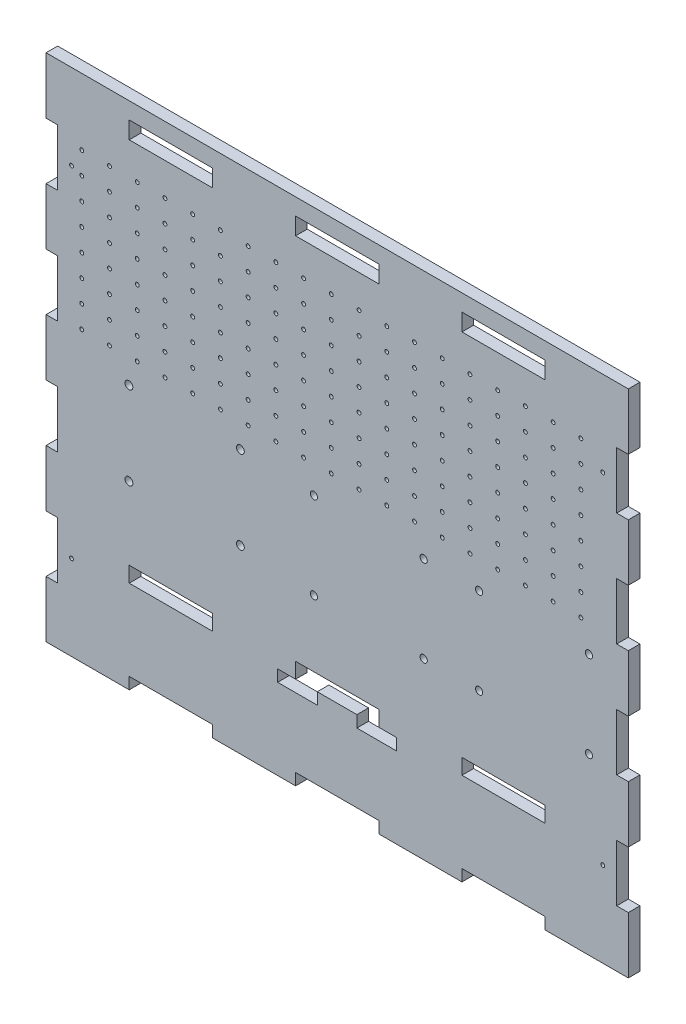
SolidWorks part; units mm, degrees
ref_plane "Front Plane" through (0, 0, 0) normal (0, 0, 1) x (1, 0, 0)
ref_plane "Top Plane" through (0, 0, 0) normal (0, 1, 0) x (1, 0, 0)
ref_plane "Right Plane" through (0, 0, 0) normal (1, 0, 0) x (0, 0, -1)
sketch "Sketch1" plane through (0, 0, 0) normal (0, 0, 1) x (1, 0, 0)
  line L1 (-127.8759, 139.2641) -> (138.8241, 139.2641)
  line L2 (-127.8759, 139.2641) -> (-127.8759, -84.2559)
  line L3 (-127.8759, -84.2559) -> (138.8241, -84.2559)
  line L4 (138.8241, 139.2641) -> (138.8241, -84.2559)
  dimension "D1" = 266.7
  dimension "D2" = 223.52
extrude "Boss-Extrude1" add sketch "Sketch1" along normal blind 5.334
sketch "Sketch2" plane through (0, 0, 5.334) normal (0, 0, 1) x (1, 0, 0)
  line L0 (-127.8759, -84.2559) -> (138.8241, -84.2559) construction
  line L1 (-89.7759, -84.2559) -> (-51.6759, -84.2559)
  line L2 (-89.7759, -84.2559) -> (-89.7759, -78.9219)
  line L3 (-89.7759, -78.9219) -> (-51.6759, -78.9219)
  line L4 (-51.6759, -84.2559) -> (-51.6759, -78.9219)
  line L5 (-89.7759, -78.9219) -> (-127.8759, -78.9219) construction
  line L6 (-13.5759, -84.2559) -> (24.5241, -84.2559)
  line L7 (-13.5759, -84.2559) -> (-13.5759, -78.9219)
  line L8 (-13.5759, -78.9219) -> (24.5241, -78.9219)
  line L9 (24.5241, -84.2559) -> (24.5241, -78.9219)
  line L10 (62.6241, -84.2559) -> (100.7241, -84.2559)
  line L11 (62.6241, -84.2559) -> (62.6241, -78.9219)
  line L12 (62.6241, -78.9219) -> (100.7241, -78.9219)
  line L13 (100.7241, -84.2559) -> (100.7241, -78.9219)
  line L14 (-127.8759, 139.2641) -> (-127.8759, -84.2559) construction
  line L15 (-51.6759, -78.9219) -> (-13.5759, -78.9219) construction
  line L16 (24.5241, -78.9219) -> (62.6241, -78.9219) construction
  line L17 (62.6241, -78.9219) -> (62.364, -79.7896) construction
  line L18 (100.7241, -78.9219) -> (138.8241, -78.9219) construction
  line L19 (138.8241, -84.2559) -> (138.8241, 139.2641) construction
  line L20 (-127.8759, 27.5041) -> (138.8241, 27.5041) construction
  line L21 (100.7241, 139.2641) -> (100.7241, 133.9301)
  line L22 (62.6241, 133.9301) -> (100.7241, 133.9301)
  line L23 (62.6241, 139.2641) -> (62.6241, 133.9301)
  line L24 (24.5241, 139.2641) -> (24.5241, 133.9301)
  line L25 (-13.5759, 133.9301) -> (24.5241, 133.9301)
  line L26 (-13.5759, 139.2641) -> (-13.5759, 133.9301)
  line L27 (-51.6759, 139.2641) -> (-51.6759, 133.9301)
  line L28 (-89.7759, 133.9301) -> (-51.6759, 133.9301)
  line L29 (-89.7759, 139.2641) -> (-89.7759, 133.9301)
  line L30 (62.6241, 139.2641) -> (100.7241, 139.2641)
  line L31 (-13.5759, 139.2641) -> (24.5241, 139.2641)
  line L32 (-89.7759, 139.2641) -> (-51.6759, 139.2641)
  dimension "D1" = 5.334
extrude "Cut-Extrude1" cut sketch "Sketch2" against normal through all
sketch "Sketch5" plane through (0, 0, 5.334) normal (0, 0, 1) x (1, 0, 0)
  line L0 (-51.6759, -34.8224) -> (-13.5759, -34.8224) construction
  line L1 (-89.7759, -34.8224) -> (-51.6759, -34.8224)
  line L2 (-89.7759, -34.8224) -> (-89.7759, -41.9344)
  line L3 (-89.7759, -41.9344) -> (-51.6759, -41.9344)
  line L4 (-51.6759, -34.8224) -> (-51.6759, -41.9344)
  line L5 (-13.5759, -34.8224) -> (24.5241, -34.8224)
  line L6 (-13.5759, -34.8224) -> (-13.5759, -41.9344)
  line L7 (-13.5759, -41.9344) -> (24.5241, -41.9344)
  line L8 (24.5241, -34.8224) -> (24.5241, -41.9344)
  line L9 (62.6241, -34.8224) -> (100.7241, -34.8224)
  line L10 (62.6241, -34.8224) -> (62.6241, -41.9344)
  line L11 (62.6241, -41.9344) -> (100.7241, -41.9344)
  line L12 (100.7241, -34.8224) -> (100.7241, -41.9344)
  line L13 (-51.6759, -41.9344) -> (-13.5759, -41.9344) construction
  line L14 (24.5241, -34.8224) -> (62.6241, -34.8224) construction
  line L15 (24.5241, -41.9344) -> (62.6241, -41.9344) construction
  line L16 (-89.7759, -34.8224) -> (-127.8759, -34.8224) construction
  line L17 (-127.8759, 139.2641) -> (-127.8759, -84.2559) construction
  line L18 (-89.7759, -41.9344) -> (-127.8759, -41.9344) construction
  line L19 (100.7241, -34.8224) -> (138.8241, -34.8224) construction
  line L20 (138.8241, -84.2559) -> (138.8241, 139.2641) construction
  line L21 (100.7241, -41.9344) -> (138.8241, -41.9344) construction
  dimension "D1" = 7.112
extrude "Cut-Extrude3" cut sketch "Sketch5" against normal through all
sketch "Sketch8" plane through (0, 0, 5.334) normal (0, 0, 1) x (1, 0, 0)
  line L0 (-13.5759, -41.9344) -> (24.5241, -41.9344) construction
  line L1 (-21.7977, -47.2684) -> (-3.6478, -47.2684)
  line L2 (-21.7977, -47.2684) -> (-21.7977, -41.9344)
  line L3 (-21.7977, -41.9344) -> (-3.6478, -41.9344)
  line L4 (-3.6478, -47.2684) -> (-3.6478, -41.9344)
  line L5 (-3.6478, -47.2684) -> (14.5022, -47.2684) construction
  line L6 (14.5022, -41.9344) -> (32.6521, -41.9344)
  line L7 (14.5022, -41.9344) -> (14.5022, -47.2684)
  line L8 (14.5022, -47.2684) -> (32.6521, -47.2684)
  line L9 (32.6521, -41.9344) -> (32.6521, -47.2684)
  line L10 (14.5022, -47.2684) -> (14.3218, -49.4005) construction
  line L11 (14.5022, -41.9344) -> (-3.6478, -41.9344) construction
  line L12 (62.6241, -34.8224) -> (62.6241, -41.9344) construction
  line L13 (-51.6759, -41.9344) -> (-51.6759, -34.8224) construction
  dimension "D1" = 5.334
  dimension "D2" = 29.972
  dimension "D3" = 29.8782
extrude "Cut-Extrude6" cut sketch "Sketch8" against normal through all
sketch "Sketch9" plane through (0, 0, 5.334) normal (0, 0, 1) x (1, 0, 0)
  line L0 (-111.5143, 118.9789) -> (-98.8143, 118.9789) construction
  line L1 (-111.5143, 108.8189) -> (-98.8143, 108.8189) construction
  line L2 (-111.5143, 98.6589) -> (-98.8143, 98.6589) construction
  line L3 (-111.5143, 88.4989) -> (-98.8143, 88.4989) construction
  line L4 (-111.5143, 78.3389) -> (-98.8143, 78.3389) construction
  line L5 (-111.5143, 68.1789) -> (-98.8143, 68.1789) construction
  line L6 (-111.5143, 58.0189) -> (-98.8143, 58.0189) construction
  line L7 (-111.5143, 47.8589) -> (-98.8143, 47.8589) construction
  line L8 (-111.5143, 118.9789) -> (-111.5143, 108.8189) construction
  circle A0 centre (-111.5143, 118.9789) radius 0.889
  circle A1 centre (-98.8143, 118.9789) radius 0.889
  circle A2 centre (-86.1143, 118.9789) radius 0.889
  circle A3 centre (-73.4143, 118.9789) radius 0.889
  circle A4 centre (-60.7143, 118.9789) radius 0.889
  circle A5 centre (-48.0143, 118.9789) radius 0.889
  circle A6 centre (-35.3143, 118.9789) radius 0.889
  circle A7 centre (-22.6143, 118.9789) radius 0.889
  circle A8 centre (-9.9143, 118.9789) radius 0.889
  circle A9 centre (2.7857, 118.9789) radius 0.889
  circle A10 centre (15.4857, 118.9789) radius 0.889
  circle A11 centre (28.1857, 118.9789) radius 0.889
  circle A12 centre (40.8857, 118.9789) radius 0.889
  circle A13 centre (53.5857, 118.9789) radius 0.889
  circle A14 centre (66.2857, 118.9789) radius 0.889
  circle A15 centre (78.9857, 118.9789) radius 0.889
  circle A16 centre (91.6857, 118.9789) radius 0.889
  circle A17 centre (104.3857, 118.9789) radius 0.889
  circle A18 centre (117.0857, 118.9789) radius 0.889
  circle A19 centre (-111.5143, 108.8189) radius 0.889
  circle A20 centre (-98.8143, 108.8189) radius 0.889
  circle A21 centre (-86.1143, 108.8189) radius 0.889
  circle A22 centre (-73.4143, 108.8189) radius 0.889
  circle A23 centre (-60.7143, 108.8189) radius 0.889
  circle A24 centre (-48.0143, 108.8189) radius 0.889
  circle A25 centre (-35.3143, 108.8189) radius 0.889
  circle A26 centre (-22.6143, 108.8189) radius 0.889
  circle A27 centre (-9.9143, 108.8189) radius 0.889
  circle A28 centre (2.7857, 108.8189) radius 0.889
  circle A29 centre (15.4857, 108.8189) radius 0.889
  circle A30 centre (28.1857, 108.8189) radius 0.889
  circle A31 centre (40.8857, 108.8189) radius 0.889
  circle A32 centre (53.5857, 108.8189) radius 0.889
  circle A33 centre (66.2857, 108.8189) radius 0.889
  circle A34 centre (78.9857, 108.8189) radius 0.889
  circle A35 centre (91.6857, 108.8189) radius 0.889
  circle A36 centre (104.3857, 108.8189) radius 0.889
  circle A37 centre (117.0857, 108.8189) radius 0.889
  circle A38 centre (-111.5143, 98.6589) radius 0.889
  circle A39 centre (-98.8143, 98.6589) radius 0.889
  circle A40 centre (-86.1143, 98.6589) radius 0.889
  circle A41 centre (-73.4143, 98.6589) radius 0.889
  circle A42 centre (-60.7143, 98.6589) radius 0.889
  circle A43 centre (-48.0143, 98.6589) radius 0.889
  circle A44 centre (-35.3143, 98.6589) radius 0.889
  circle A45 centre (-22.6143, 98.6589) radius 0.889
  circle A46 centre (-9.9143, 98.6589) radius 0.889
  circle A47 centre (2.7857, 98.6589) radius 0.889
  circle A48 centre (15.4857, 98.6589) radius 0.889
  circle A49 centre (28.1857, 98.6589) radius 0.889
  circle A50 centre (40.8857, 98.6589) radius 0.889
  circle A51 centre (53.5857, 98.6589) radius 0.889
  circle A52 centre (66.2857, 98.6589) radius 0.889
  circle A53 centre (78.9857, 98.6589) radius 0.889
  circle A54 centre (91.6857, 98.6589) radius 0.889
  circle A55 centre (104.3857, 98.6589) radius 0.889
  circle A56 centre (117.0857, 98.6589) radius 0.889
  circle A57 centre (-111.5143, 88.4989) radius 0.889
  circle A58 centre (-98.8143, 88.4989) radius 0.889
  circle A59 centre (-86.1143, 88.4989) radius 0.889
  circle A60 centre (-73.4143, 88.4989) radius 0.889
  circle A61 centre (-60.7143, 88.4989) radius 0.889
  circle A62 centre (-48.0143, 88.4989) radius 0.889
  circle A63 centre (-35.3143, 88.4989) radius 0.889
  circle A64 centre (-22.6143, 88.4989) radius 0.889
  circle A65 centre (-9.9143, 88.4989) radius 0.889
  circle A66 centre (2.7857, 88.4989) radius 0.889
  circle A67 centre (15.4857, 88.4989) radius 0.889
  circle A68 centre (28.1857, 88.4989) radius 0.889
  circle A69 centre (40.8857, 88.4989) radius 0.889
  circle A70 centre (53.5857, 88.4989) radius 0.889
  circle A71 centre (66.2857, 88.4989) radius 0.889
  circle A72 centre (78.9857, 88.4989) radius 0.889
  circle A73 centre (91.6857, 88.4989) radius 0.889
  circle A74 centre (104.3857, 88.4989) radius 0.889
  circle A75 centre (117.0857, 88.4989) radius 0.889
  circle A76 centre (-111.5143, 78.3389) radius 0.889
  circle A77 centre (-98.8143, 78.3389) radius 0.889
  circle A78 centre (-86.1143, 78.3389) radius 0.889
  circle A79 centre (-73.4143, 78.3389) radius 0.889
  circle A80 centre (-60.7143, 78.3389) radius 0.889
  circle A81 centre (-48.0143, 78.3389) radius 0.889
  circle A82 centre (-35.3143, 78.3389) radius 0.889
  circle A83 centre (-22.6143, 78.3389) radius 0.889
  circle A84 centre (-9.9143, 78.3389) radius 0.889
  circle A85 centre (2.7857, 78.3389) radius 0.889
  circle A86 centre (15.4857, 78.3389) radius 0.889
  circle A87 centre (28.1857, 78.3389) radius 0.889
  circle A88 centre (40.8857, 78.3389) radius 0.889
  circle A89 centre (53.5857, 78.3389) radius 0.889
  circle A90 centre (66.2857, 78.3389) radius 0.889
  circle A91 centre (78.9857, 78.3389) radius 0.889
  circle A92 centre (91.6857, 78.3389) radius 0.889
  circle A93 centre (104.3857, 78.3389) radius 0.889
  circle A94 centre (117.0857, 78.3389) radius 0.889
  circle A95 centre (-111.5143, 68.1789) radius 0.889
  circle A96 centre (-98.8143, 68.1789) radius 0.889
  circle A97 centre (-86.1143, 68.1789) radius 0.889
  circle A98 centre (-73.4143, 68.1789) radius 0.889
  circle A99 centre (-60.7143, 68.1789) radius 0.889
  circle A100 centre (-48.0143, 68.1789) radius 0.889
  circle A101 centre (-35.3143, 68.1789) radius 0.889
  circle A102 centre (-22.6143, 68.1789) radius 0.889
  circle A103 centre (-9.9143, 68.1789) radius 0.889
  circle A104 centre (2.7857, 68.1789) radius 0.889
  circle A105 centre (15.4857, 68.1789) radius 0.889
  circle A106 centre (28.1857, 68.1789) radius 0.889
  circle A107 centre (40.8857, 68.1789) radius 0.889
  circle A108 centre (53.5857, 68.1789) radius 0.889
  circle A109 centre (66.2857, 68.1789) radius 0.889
  circle A110 centre (78.9857, 68.1789) radius 0.889
  circle A111 centre (91.6857, 68.1789) radius 0.889
  circle A112 centre (104.3857, 68.1789) radius 0.889
  circle A113 centre (117.0857, 68.1789) radius 0.889
  circle A114 centre (-111.5143, 58.0189) radius 0.889
  circle A115 centre (-98.8143, 58.0189) radius 0.889
  circle A116 centre (-86.1143, 58.0189) radius 0.889
  circle A117 centre (-73.4143, 58.0189) radius 0.889
  circle A118 centre (-60.7143, 58.0189) radius 0.889
  circle A119 centre (-48.0143, 58.0189) radius 0.889
  circle A120 centre (-35.3143, 58.0189) radius 0.889
  circle A121 centre (-22.6143, 58.0189) radius 0.889
  circle A122 centre (-9.9143, 58.0189) radius 0.889
  circle A123 centre (2.7857, 58.0189) radius 0.889
  circle A124 centre (15.4857, 58.0189) radius 0.889
  circle A125 centre (28.1857, 58.0189) radius 0.889
  circle A126 centre (40.8857, 58.0189) radius 0.889
  circle A127 centre (53.5857, 58.0189) radius 0.889
  circle A128 centre (66.2857, 58.0189) radius 0.889
  circle A129 centre (78.9857, 58.0189) radius 0.889
  circle A130 centre (91.6857, 58.0189) radius 0.889
  circle A131 centre (104.3857, 58.0189) radius 0.889
  circle A132 centre (117.0857, 58.0189) radius 0.889
  circle A133 centre (-111.5143, 47.8589) radius 0.889
  circle A134 centre (-98.8143, 47.8589) radius 0.889
  circle A135 centre (-86.1143, 47.8589) radius 0.889
  circle A136 centre (-73.4143, 47.8589) radius 0.889
  circle A137 centre (-60.7143, 47.8589) radius 0.889
  circle A138 centre (-48.0143, 47.8589) radius 0.889
  circle A139 centre (-35.3143, 47.8589) radius 0.889
  circle A140 centre (-22.6143, 47.8589) radius 0.889
  circle A141 centre (-9.9143, 47.8589) radius 0.889
  circle A142 centre (2.7857, 47.8589) radius 0.889
  circle A143 centre (15.4857, 47.8589) radius 0.889
  circle A144 centre (28.1857, 47.8589) radius 0.889
  circle A145 centre (40.8857, 47.8589) radius 0.889
  circle A146 centre (53.5857, 47.8589) radius 0.889
  circle A147 centre (66.2857, 47.8589) radius 0.889
  circle A148 centre (78.9857, 47.8589) radius 0.889
  circle A149 centre (91.6857, 47.8589) radius 0.889
  circle A150 centre (104.3857, 47.8589) radius 0.889
  circle A151 centre (117.0857, 47.8589) radius 0.889
  dimension "D1" = 19
  dimension "D5" = 1.778
  dimension "D2" = 12.7
  dimension "D4" = 10.16
  dimension "D3" = 8
extrude "Cut-Extrude7" cut sketch "Sketch9" against normal through all
sketch "Sketch10" plane through (0, 139.2641, 0) normal (0, 1, 0) x (1, 0, 0)
  line L0 (-13.5759, -5.334) -> (-51.6759, -5.334) construction
  line L1 (-51.6759, 0) -> (-13.5759, 0)
  line L2 (-51.6759, 0) -> (-51.6759, -5.334)
  line L3 (-51.6759, -5.334) -> (-13.5759, -5.334)
  line L4 (-13.5759, 0) -> (-13.5759, -5.334)
extrude "Boss-Extrude2" add sketch "Sketch10" along normal blind 10.16
sketch "Sketch12" plane through (-51.6759, 0, 0) normal (-1, 0, 0) x (0, 0, 1)
  line L0 (0, 133.9301) -> (0, 149.4241) construction
  line L1 (5.334, 149.4241) -> (0, 149.4241)
  line L2 (5.334, 149.4241) -> (5.334, 141.8041)
  line L3 (5.334, 141.8041) -> (0, 141.8041)
  line L4 (0, 149.4241) -> (0, 141.8041)
  dimension "D1" = 7.62
extrude "Boss-Extrude3" add sketch "Sketch12" along normal blind 76.2 and the other way blind 190.5
sketch "Sketch13" plane through (0, 139.2641, 0) normal (0, 1, 0) x (1, 0, 0)
  line L1 (-127.8759, 0) -> (-89.7759, 0)
  line L2 (-127.8759, 0) -> (-127.8759, -5.334)
  line L3 (-127.8759, -5.334) -> (-89.7759, -5.334)
  line L4 (-89.7759, 0) -> (-89.7759, -5.334)
extrude "Boss-Extrude4" add sketch "Sketch13" along normal blind 2.54
sketch "Sketch14" plane through (0, 139.2641, 0) normal (0, 1, 0) x (1, 0, 0)
  line L1 (24.5241, 0) -> (62.6241, 0)
  line L2 (24.5241, 0) -> (24.5241, -5.334)
  line L3 (24.5241, -5.334) -> (62.6241, -5.334)
  line L4 (62.6241, 0) -> (62.6241, -5.334)
extrude "Boss-Extrude5" add sketch "Sketch14" along normal blind 2.54
sketch "Sketch15" plane through (0, 139.2641, 0) normal (0, 1, 0) x (1, 0, 0)
  line L1 (100.7241, 0) -> (138.8241, 0)
  line L2 (100.7241, 0) -> (100.7241, -5.334)
  line L3 (100.7241, -5.334) -> (138.8241, -5.334)
  line L4 (138.8241, 0) -> (138.8241, -5.334)
extrude "Boss-Extrude6" add sketch "Sketch15" along normal blind 2.54
sketch "Sketch16" plane through (0, 0, 5.334) normal (0, 0, 1) x (1, 0, 0)
  line L0 (-127.8759, 149.4241) -> (-127.8759, -84.2559) construction
  line L1 (-127.8759, -32.327) -> (-122.5419, -32.327)
  line L2 (-127.8759, -32.327) -> (-127.8759, -58.2914)
  line L3 (-127.8759, -58.2914) -> (-122.5419, -58.2914)
  line L4 (-122.5419, -32.327) -> (-122.5419, -58.2914)
  line L5 (-122.5419, -32.327) -> (-122.5419, -6.3625) construction
  line L6 (-127.8759, 19.6019) -> (-122.5419, 19.6019)
  line L7 (-122.5419, -58.2914) -> (-122.5419, -84.2559) construction
  line L8 (-127.8759, -84.2559) -> (-89.7759, -84.2559) construction
  line L9 (-127.8759, 19.6019) -> (-127.8759, -6.3625)
  line L10 (-127.8759, -6.3625) -> (-122.5419, -6.3625)
  line L11 (-122.5419, 19.6019) -> (-122.5419, -6.3625)
  line L12 (-122.5419, 19.6019) -> (-122.5419, 45.5664) construction
  line L13 (5.4741, -78.9219) -> (5.4741, 149.4241) construction
  line L14 (-127.8759, 71.5308) -> (-122.5419, 71.5308)
  line L15 (-127.8759, 71.5308) -> (-127.8759, 45.5664)
  line L16 (-127.8759, 45.5664) -> (-122.5419, 45.5664)
  line L17 (-122.5419, 71.5308) -> (-122.5419, 45.5664)
  line L18 (-122.5419, 71.5308) -> (-122.5419, 97.4953) construction
  line L19 (24.5241, -78.9219) -> (-13.5759, -78.9219) construction
  line L20 (-127.8759, 97.4953) -> (-122.5419, 97.4953)
  line L21 (-127.8759, 97.4953) -> (-127.8759, 123.4597)
  line L22 (-127.8759, 123.4597) -> (-122.5419, 123.4597)
  line L23 (-122.5419, 97.4953) -> (-122.5419, 123.4597)
  line L24 (-122.5419, 123.4597) -> (-122.5419, 149.4241) construction
  line L25 (-127.8759, 149.4241) -> (138.8241, 149.4241) construction
  line L26 (133.4901, 123.4597) -> (133.4901, 149.4241) construction
  line L27 (133.4901, 71.5308) -> (133.4901, 97.4953) construction
  line L28 (133.4901, 19.6019) -> (133.4901, 45.5664) construction
  line L29 (133.4901, -58.2914) -> (133.4901, -84.2559) construction
  line L30 (133.4901, -32.327) -> (133.4901, -6.3625) construction
  line L31 (133.4901, 97.4953) -> (133.4901, 123.4597)
  line L32 (138.8241, 123.4597) -> (133.4901, 123.4597)
  line L33 (138.8241, 97.4953) -> (138.8241, 123.4597)
  line L34 (138.8241, 97.4953) -> (133.4901, 97.4953)
  line L35 (133.4901, 71.5308) -> (133.4901, 45.5664)
  line L36 (138.8241, 45.5664) -> (133.4901, 45.5664)
  line L37 (138.8241, 71.5308) -> (138.8241, 45.5664)
  line L38 (138.8241, 71.5308) -> (133.4901, 71.5308)
  line L39 (133.4901, 19.6019) -> (133.4901, -6.3625)
  line L40 (138.8241, -6.3625) -> (133.4901, -6.3625)
  line L41 (138.8241, 19.6019) -> (138.8241, -6.3625)
  line L42 (138.8241, 19.6019) -> (133.4901, 19.6019)
  line L43 (133.4901, -32.327) -> (133.4901, -58.2914)
  line L44 (138.8241, -58.2914) -> (133.4901, -58.2914)
  line L45 (138.8241, -32.327) -> (138.8241, -58.2914)
  line L46 (138.8241, -32.327) -> (133.4901, -32.327)
  dimension "D1" = 5.334
extrude "Cut-Extrude9" cut sketch "Sketch16" against normal through all
sketch "Sketch17" plane through (0, 0, 5.334) normal (0, 0, 1) x (1, 0, 0)
  line L1 (133.4901, 71.5308) -> (133.4901, 45.5664) construction
  circle A0 centre (120.7901, 35.1589) radius 1.651
  circle A1 centre (117.0857, 47.8589) radius 0.889 construction
  circle A2 centre (70.4981, 35.1589) radius 1.651
  circle A3 centre (70.4981, -4.4651) radius 1.651
  circle A4 centre (120.7901, -4.4651) radius 1.651
  circle A5 centre (45.0981, 35.1589) radius 1.651
  circle A6 centre (-5.1939, 35.1589) radius 1.651
  circle A7 centre (-5.1939, -4.4651) radius 1.651
  circle A8 centre (45.0981, -4.4651) radius 1.651
  dimension "D1" = 12.7
  dimension "D2" = 12.7
  dimension "D3" = 2
  dimension "D4" = 2
  dimension "D5" = 2
  dimension "D6" = 2
  dimension "D7" = 2
extrude "Cut-Extrude10" cut sketch "Sketch17" against normal through all
sketch "Sketch18" plane through (0, 0, 5.334) normal (0, 0, 1) x (1, 0, 0)
  line L0 (133.4901, 123.4597) -> (133.4901, 97.4953) construction
  line L1 (133.4901, 110.4775) -> (-122.5419, 110.4775) construction
  line L2 (-122.5419, 97.4953) -> (-122.5419, 123.4597) construction
  line L3 (-122.5419, -45.3092) -> (133.4901, -45.3092) construction
  line L4 (-122.5419, -58.2914) -> (-122.5419, -32.327) construction
  line L5 (133.4901, -32.327) -> (133.4901, -58.2914) construction
  line L6 (138.8241, 32.5841) -> (-127.8759, 32.5841) construction
  line L7 (138.8241, 19.6019) -> (138.8241, 45.5664) construction
  line L8 (-127.8759, 45.5664) -> (-127.8759, 19.6019) construction
  line L9 (5.4741, 149.4241) -> (5.4741, -78.9219) construction
  line L10 (-127.8759, 149.4241) -> (138.8241, 149.4241) construction
  line L11 (24.5241, -78.9219) -> (-13.5759, -78.9219) construction
  circle A0 centre (127.1401, 110.4775) radius 0.889
  circle A1 centre (-116.1919, 110.4775) radius 0.889
  circle A2 centre (-116.1919, -45.3092) radius 0.889
  circle A3 centre (127.1401, -45.3092) radius 0.889
  dimension "D3" = 1.778
  dimension "D1" = 0
  dimension "D2" = 6.35
extrude "Cut-Extrude11" cut sketch "Sketch18" against normal through all
sketch "Sketch19" plane through (0, 0, 0) normal (0, 0, -1) x (-1, 0, 0)
  circle A0 centre (89.9029, 36.5559) radius 1.778 construction
  circle A1 centre (89.9029, -1.5441) radius 1.778 construction
  circle A2 centre (38.8489, -1.5441) radius 1.778 construction
  circle A3 centre (38.8489, 36.5559) radius 1.778 construction
  circle A4 centre (89.9029, 36.5559) radius 1.778
  circle A5 centre (89.9029, -1.5441) radius 1.778
  circle A6 centre (38.8489, -1.5441) radius 1.778
  circle A7 centre (38.8489, 36.5559) radius 1.778
extrude "Cut-Extrude12" cut sketch "Sketch19" against normal through all
equation "\"MDF\"= .21in"
equation "\"Foamcore\"= .13in"
equation "\"Gmaterial\"= \"MDF\""
equation "\"D1@Boss-Extrude1\"=\"MDF\""
equation "\"D1@Sketch2\"=\"MDF\""
equation "\"D1@Sketch5\"=\"MDF\"+0.07"
equation "\"D1@Sketch8\"=\"MDF\""
equation "\"D1@Sketch16\"=\"MDF\""
